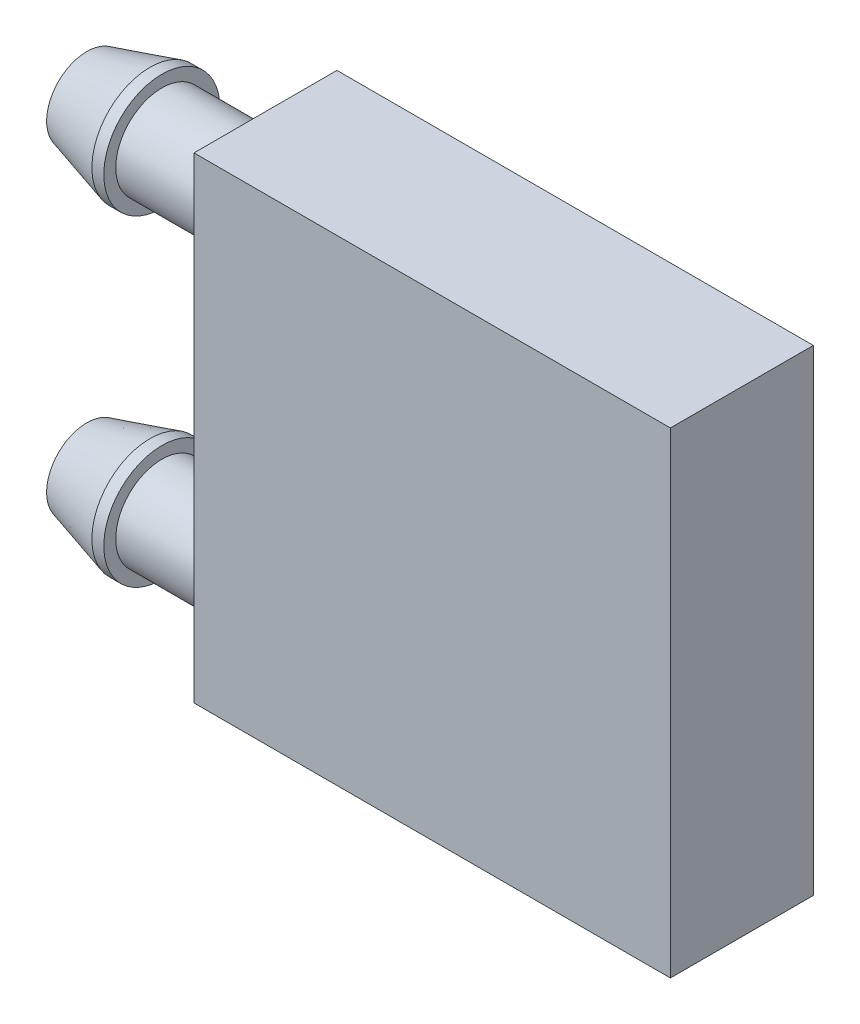
SolidWorks part; units mm, degrees
material "6061 Alloy"
ref_plane "Front Plane" through (0, 0, 0) normal (0, 0, 1) x (1, 0, 0)
ref_plane "Top Plane" through (0, 0, 0) normal (0, 1, 0) x (1, 0, 0)
ref_plane "Right Plane" through (0, 0, 0) normal (1, 0, 0) x (0, 0, -1)
sketch "Base" plane through (0, 0, 0) normal (0, 0, 1) x (1, 0, 0)
  line L7 (-30, 20) -> (10, 20)
  line L8 (-30, 20) -> (-30, -20)
  line L9 (-30, -20) -> (10, -20)
  line L10 (10, 20) -> (10, -20)
  point P0 (0, 0)
  dimension "D1" = 40
  dimension "D2" = 40
extrude "Boss-Extrude Base" add sketch "Base" along normal blind 6 and the other way blind 6
sketch "Port Profile" plane through (0, 0, 0) normal (0, 0, 1) x (1, 0, 0)
  line L0 (-30, 16.375) -> (-45, 16.375)
  line L12 (-30, 13.5) -> (-45, 13.5) construction
  line L13 (-45, 16.375) -> (-45, 16.875)
  line L17 (-30, 20) -> (-30, -20) construction
  line L18 (-45, 16.875) -> (-39.7, 18.375)
  line L19 (-39.7, 18.375) -> (-38.7, 18.375)
  line L20 (-38.7, 18.375) -> (-38.7, 17.375)
  line L21 (-38.7, 17.375) -> (-31, 17.375)
  line L22 (-31, 17.375) -> (-31, 18.375)
  line L23 (-31, 18.375) -> (-30, 18.375)
  line L24 (-30, 18.375) -> (-30, 16.375)
  line L25 (-30, 18.375) -> (-45, 18.375) construction
  line L26 (-30, 0) -> (-46.5031, 0) construction
  point P24 (-38.7, 17.875)
  dimension "D2" = 1
  dimension "D3" = 1
  dimension "D4" = 13.5
  dimension "D9" = 2
  dimension "D10" = 1
  dimension "D12" = 8.7
  dimension "D13" = 0.5
  dimension "D14" = 15
  dimension "D15" = 2.875
revolve "Revolve Port" add sketch "Port Profile" angle 360 about L12
mirror "Mirror Port" about plane through (0, 0, 0) normal (0, 1, 0) of "Revolve Port"
